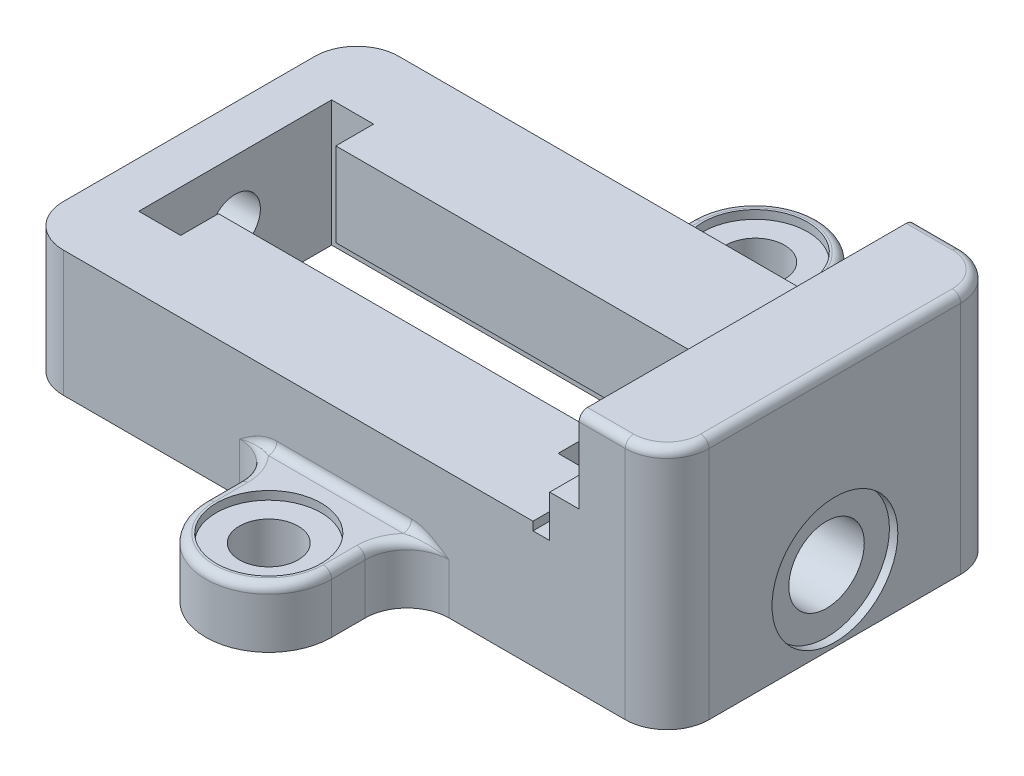
SolidWorks part; units mm, degrees
material "HT200"
ref_plane "前视基准面" through (0, 0, 0) normal (0, 0, 1) x (1, 0, 0)
ref_plane "上视基准面" through (0, 0, 0) normal (0, 1, 0) x (1, 0, 0)
ref_plane "右视基准面" through (0, 0, 0) normal (1, 0, 0) x (0, 0, -1)
sketch "草图1" plane through (0, 0, 0) normal (0, 1, 0) x (1, 0, 0)
  line L1 (77, -40) -> (-77, -40)
  line L2 (77, -40) -> (77, 40)
  line L3 (77, 40) -> (-77, 40)
  line L4 (-77, -40) -> (-77, 40)
  line L5 (77, -40) -> (-77, 40) construction
  line L6 (77, 40) -> (-77, -40) construction
  point P0 (0, 0)
  dimension "D1" = 154
  dimension "D2" = 80
extrude "凸台-拉伸1" add sketch "草图1" along normal blind 30
sketch "草图2" plane through (0, 30, 0) normal (0, 1, 0) x (1, 0, 0)
  line L0 (-79.2153, 0) -> (84.7401, 0) construction
  line L1 (-66, -23) -> (-66, 23)
  line L2 (-66, 23) -> (49, 23)
  line L3 (49, 23) -> (49, -23)
  line L4 (77, -40) -> (77, 40) construction
  line L5 (-66, -23) -> (49, -23)
  point P10 (49, 0)
  point P11 (-66, 0)
  dimension "D1" = 115
  dimension "D2" = 46
  dimension "D3" = 28
extrude "切除-拉伸1" cut sketch "草图2" against normal through all
sketch "草图3" plane through (0, 30, 0) normal (0, 1, 0) x (1, 0, 0)
  line L1 (-56, 23) -> (-56, 14)
  line L2 (49, 23) -> (-66, 23) construction
  line L3 (-56, 14) -> (34, 14)
  line L4 (34, 14) -> (34, 23)
  line L5 (34, 23) -> (-56, 23)
  line L6 (-79.2153, 0) -> (84.7401, 0) construction
  line L7 (-79.2153, 0) -> (84.7401, 0) construction
  line L8 (49, 23) -> (49, -23) construction
  dimension "D1" = 90
  dimension "D2" = 15
  dimension "D3" = 28
extrude "凸台-拉伸2" add sketch "草图3" against normal blind 20
mirror "镜向1" about plane through (0, 0, 0) normal (0, 0, 1) of "凸台-拉伸2"
sketch "草图4" plane through (0, 0, 0) normal (0, -1, 0) x (1, 0, 0)
  line L0 (0, 2.5085) -> (0, 65.1335) construction
  line L1 (-15, 58) -> (-15, 50)
  line L3 (15, 58) -> (15, 50)
  line L4 (-77, 40) -> (77, 40) construction
  line L6 (-79.2153, 0) -> (84.7401, 0) construction
  line L7 (-79.2153, 0) -> (84.7401, 0) construction
  line L8 (-25, 40) -> (25, 40)
  line L9 (-25, -40) -> (25, -40)
  line L10 (-15, -58) -> (-15, -50)
  line L11 (15, -58) -> (15, -50)
  circle A0 centre (0, 58) radius 7
  arc A1 (15, 58) -> (-15, 58) centre (0, 58) ccw
  arc A2 (-25, 40) -> (-15, 50) centre (-25, 50) ccw
  arc A3 (25, 40) -> (15, 50) centre (25, 50) cw
  arc A4 (-25, -40) -> (-15, -50) centre (-25, -50) cw
  arc A5 (15, -58) -> (-15, -58) centre (0, -58) cw
  arc A6 (25, -40) -> (15, -50) centre (25, -50) ccw
  circle A7 centre (0, -58) radius 7
  dimension "D1" = 10
  dimension "D3" = 14
  dimension "D4" = 30
  dimension "D2" = 116
extrude "凸台-拉伸3" add sketch "草图4" against normal blind 14
sketch "草图6" plane through (0, 14, 0) normal (0, 1, 0) x (1, 0, 0)
  circle A0 centre (0, -58) radius 12.5
  dimension "D1" = 25
extrude "切除-拉伸2" cut sketch "草图6" against normal blind 2
mirror "镜向2" about plane through (0, 0, 0) normal (0, 0, 1) of "切除-拉伸2"
sketch "草图7" plane through (-77, 0, 0) normal (-1, 0, 0) x (0, 0, 1)
  line L0 (0, -3.5632) -> (0, 34.1794) construction
  line L1 (-40, 0) -> (40, 0) construction
  circle A0 centre (0, 16) radius 6
  dimension "D1" = 12
  dimension "D2" = 16
extrude "切除-拉伸3" cut sketch "草图7" against normal up to next
sketch "草图8" plane through (77, 0, 0) normal (1, 0, 0) x (0, 0, -1)
  line L0 (0, -4.6416) -> (0, 44.9631) construction
  line L1 (-40, 0) -> (40, 0) construction
  circle A0 centre (0, 16) radius 9
  dimension "D1" = 18
  dimension "D2" = 16
extrude "切除-拉伸4" cut sketch "草图8" against normal up to next
sketch "草图10" plane through (0, 30, 0) normal (0, 1, 0) x (1, 0, 0)
  line L0 (49, 23) -> (49, -23) construction
  line L1 (49, 40) -> (49, -40)
  line L4 (-77, 40) -> (-77, -40)
  line L5 (-77, -40) -> (77, -40)
  line L6 (77, -40) -> (77, 40)
  line L7 (77, 40) -> (-77, 40)
  line L9 (49, -40) -> (77, -40)
  line L10 (77, -40) -> (77, 40)
  line L11 (77, 40) -> (49, 40)
  dimension "D1" = 0
extrude "凸台-拉伸4" add sketch "草图10" along normal blind 28
sketch "草图11" plane through (0, 58, 0) normal (0, 1, 0) x (1, 0, 0)
  line L0 (56, 40) -> (56, -40)
  line L4 (77, -40) -> (77, 40)
  line L5 (77, 40) -> (49, 40)
  line L6 (49, 40) -> (49, -40)
  line L7 (49, -40) -> (77, -40)
  line L9 (56, 40) -> (49, 40)
  line L10 (49, 40) -> (49, -40)
  line L11 (49, -40) -> (56, -40)
  dimension "D2" = 7
  dimension "D1" = 0
extrude "切除-拉伸5" cut sketch "草图11" against normal blind 20
sketch "草图12" plane through (0, 30, 0) normal (0, 1, 0) x (1, 0, 0)
  line L0 (45, 40) -> (45, 23)
  line L1 (45, -23) -> (45, -40)
  line L16 (49, 23) -> (49, 40)
  line L17 (49, 40) -> (-77, 40)
  line L18 (-77, 40) -> (-77, -40)
  line L19 (-77, -40) -> (49, -40)
  line L20 (49, -40) -> (49, -23)
  line L21 (49, -23) -> (34, -23)
  line L22 (34, -23) -> (34, -14)
  line L23 (34, -14) -> (-56, -14)
  line L24 (-56, -14) -> (-56, -23)
  line L25 (-56, -23) -> (-66, -23)
  line L26 (-66, -23) -> (-66, 23)
  line L27 (-66, 23) -> (-56, 23)
  line L28 (-56, 23) -> (-56, 14)
  line L29 (-56, 14) -> (34, 14)
  line L30 (34, 14) -> (34, 23)
  line L31 (34, 23) -> (49, 23)
  line L32 (49, 23) -> (49, 40)
  line L33 (49, 40) -> (45, 40)
  line L35 (45, -40) -> (49, -40)
  line L36 (49, -40) -> (49, -23)
  line L37 (49, -23) -> (45, -23)
  line L47 (45, 23) -> (49, 23)
  dimension "D2" = 4
  dimension "D1" = 0
extrude "切除-拉伸6" cut sketch "草图12" against normal blind 2
sketch "草图13" plane through (77, 0, 0) normal (1, 0, 0) x (0, 0, -1)
  circle A0 centre (0, 16) radius 15
  dimension "D1" = 30
extrude "切除-拉伸7" cut sketch "草图13" against normal blind 2
sketch "草图14" plane through (56, 0, 0) normal (-1, 0, 0) x (0, 0, 1)
  line L0 (-40, 38) -> (40, 38) construction
  line L1 (0, -3.2738) -> (0, 66.6656) construction
  point P0 (-20, 49)
  point P1 (20, 49)
  dimension "D1" = 11
  dimension "D2" = 40
hole_wizard "M8 螺纹孔1" positions "草图16" profile "草图15" tap size "M8" standard "GB"
sketch "草图16" plane through (56, 0, 0) normal (-1, 0, 0) x (0, 0, 1)
  point P0 (-20, 49)
  point P1 (20, 49)
sketch "草图15" plane through (56, 49, -20) normal (0, 1, 0) x (0, 0, 1)
  line L0 (0, 0) -> (0, 16.0429)
  line L1 (0, 16.0429) -> (3.4, 14)
  line L2 (3.4, 14) -> (3.4, 0)
  line L5 (3.4, 0) -> (0, 0)
  line L10 (0, 16.0429) -> (-3.4, 14) construction
  line L11 (0, -6.35) -> (0, 107.95) construction
  dimension "螺纹孔钻头直径" = 6.8
  dimension "螺纹孔钻头深度" = 14
  dimension "导头角度" = 118
cosmetic thread "孔螺蚊线1" parameters "D1"=10, "D2"=8
cosmetic thread "孔螺蚊线2" parameters "D1"=10, "D2"=8
fillet "圆角5" radius 10 4 edges at (-77, 15, 40) (-77, 15, -40) (77, 29, 40) (77, 29, -40)
fillet "圆角6" radius 2 6 edges at (-17.9289, 14, 42.9289) (-15, 14, 54) (0, 14, 73) (15, 14, 54) (0, 14, 40) (17.9289, 14, 42.9289)
fillet "圆角7" radius 2 6 edges at (17.9289, 14, -42.9289) (15, 14, -54) (0, 14, -73) (-15, 14, -54) (0, 14, -40) (-17.9289, 14, -42.9289)
fillet "圆角8" radius 2 5 edges at (61.5, 58, -40) (74.0711, 58, -37.0711) (77, 58, 0) (74.0711, 58, 37.0711) (61.5, 58, 40)
